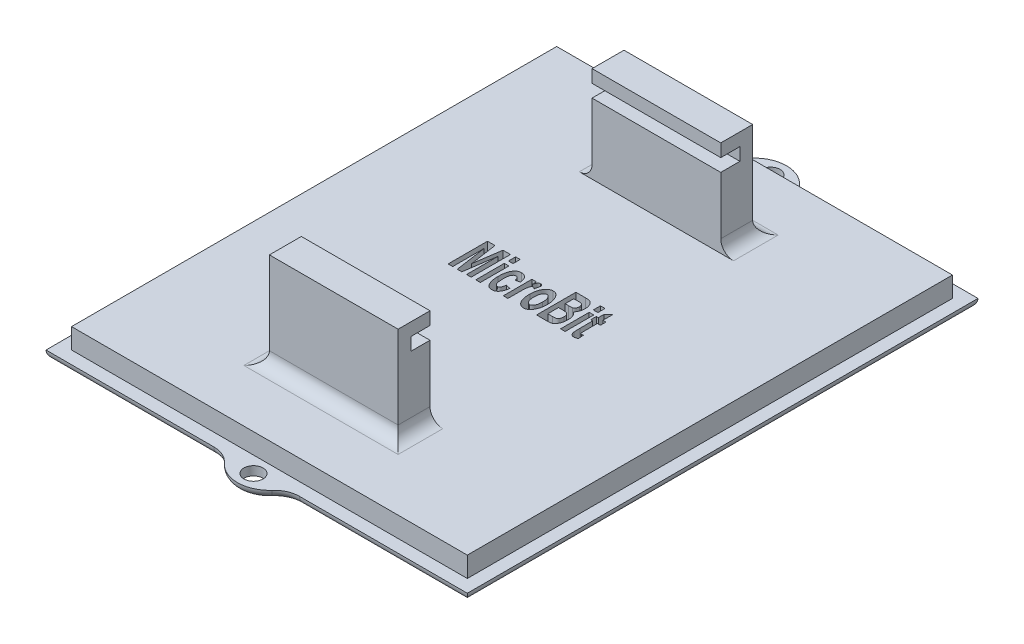
SolidWorks part; units mm, degrees
ref_plane "Front Plane" through (0, 0, 0) normal (0, 0, 1) x (1, 0, 0)
ref_plane "Top Plane" through (0, 0, 0) normal (0, 1, 0) x (1, 0, 0)
ref_plane "Right Plane" through (0, 0, 0) normal (1, 0, 0) x (0, 0, -1)
sketch "Sketch1" plane through (0, 0, 0) normal (0, 1, 0) x (1, 0, 0)
  line L0 (-31, 38) -> (31, 38)
  line L5 (-31, 38) -> (-31, -38)
  line L6 (-31, -38) -> (31, -38)
  line L7 (31, 38) -> (31, -38)
  point P11 (-31, 0)
  point P12 (0, -38)
  dimension "D3" = 76
  dimension "D4" = 62
extrude "Boss-Extrude1" add sketch "Sketch1" along normal blind 4.575
sketch "Sketch11" plane through (0, 0, 0) normal (0, -1, 0) x (-1, 0, 0)
  line L0 (-31, 38) -> (31, 38) construction
  line L1 (-33, -40) -> (33, -40)
  line L2 (-33, -40) -> (-33, 40)
  line L3 (-33, 40) -> (33, 40)
  line L4 (33, -40) -> (33, 40)
  line L5 (-31, -38) -> (-31, 38) construction
  line L6 (31, -38) -> (-31, -38) construction
  line L13 (31, 38) -> (31, -38) construction
  dimension "D1" = 2
  dimension "D2" = 2
  dimension "D3" = 2
  dimension "D4" = 2
extrude "Boss-Extrude5" add sketch "Sketch11" against normal blind 1.4
sketch "Sketch4" plane through (0, 0, 0) normal (0, 1, 0) x (1, 0, 0)
  line L2 (-31, -38) -> (31, -38) construction
  line L3 (33, -40) -> (-33, -40) construction
  line L5 (-6.7082, -40) -> (6.7082, -40)
  arc A3 (-6.7082, -40) -> (-3.7268, -41.3333) centre (-6.7082, -44) cw
  arc A4 (-3.7268, -41.3333) -> (3.7268, -41.3333) centre (0, -38) ccw
  arc A5 (3.7268, -41.3333) -> (6.7082, -40) centre (6.7082, -44) cw
  dimension "D1" = 5
  dimension "D4" = 4
extrude "Boss-Extrude3" add sketch "Sketch4" along normal blind 1.4
sketch "Sketch12" plane through (0, 1.4, 0) normal (0, 1, 0) x (1, 0, 0)
  line L0 (0, -38) -> (0, -43) construction
  line L1 (-31, -38) -> (31, -38) construction
  arc A0 (-3.7268, -41.3333) -> (3.7268, -41.3333) centre (0, -38) ccw construction
  circle A1 centre (0, -40.5) radius 1.5
  dimension "D1" = 3
extrude "Cut-Extrude3" cut sketch "Sketch12" against normal up to next
mirror "Mirror1" about plane through (0, 0, 0) normal (0, 0, 1) of "Cut-Extrude3", "Boss-Extrude3"
fillet "Fillet1" radius 1.4 12 edges at (19.8541, 0, -40) (5.0752, 0, -40.3485) (0, 0, -43) (-5.0752, 0, -40.3485) (-19.8541, 0, -40) (-33, 0, 0) (-19.8541, 0, 40) (-5.0752, 0, 40.3485) (0, 0, 43) (5.0752, 0, 40.3485) (19.8541, 0, 40) (33, 0, 0)
sketch "Sketch5" plane through (0, 4.575, 0) normal (0, 1, 0) x (1, 0, 0)
  line L0 (-15, 0) -> (15, 0) construction
  text T0 "MicroBit" font "Arial Narrow" height in points 24
  point P6 (0, 0)
  dimension "D1" = 30
extrude "Letters" cut sketch "Sketch5" against normal blind 2
sketch "Sketch21" plane through (0, 4.575, 0) normal (0, 1, 0) x (1, 0, 0)
  line L1 (-21.1498, 24.9347) -> (20.8502, 24.9347)
  line L2 (-21.1498, 24.9347) -> (-21.1498, -26.5653)
  line L3 (-21.1498, -26.5653) -> (20.8502, -26.5653)
  line L4 (20.8502, 24.9347) -> (20.8502, -26.5653)
  line L5 (-21.1498, 24.9347) -> (20.8502, -26.5653) construction
  line L6 (-21.1498, -26.5653) -> (20.8502, 24.9347) construction
  line L7 (-10.2291, -22.7722) -> (9.9294, -22.7722)
  line L8 (-10.2291, -22.7722) -> (-10.2291, -27.7722)
  line L9 (-10.2291, -27.7722) -> (9.9294, -27.7722)
  line L10 (9.9294, -22.7722) -> (9.9294, -27.7722)
  line L11 (-10.2291, -22.7722) -> (9.9294, -27.7722) construction
  line L12 (-10.2291, -27.7722) -> (9.9294, -22.7722) construction
  point P4 (-0.1498, -0.8153)
  point P9 (-0.1498, -25.2722)
  dimension "D1" = 42
  dimension "D2" = 51.5
  dimension "D3" = 5
extrude "Boss-Extrude8" add sketch "Sketch21" along normal blind 15 contours L9 L10 L7 L8
sketch "Sketch33" plane through (9.9294, 0, 0) normal (1, 0, 0) x (0, 0, -1)
  line L0 (-22.7722, 19.575) -> (-22.7722, 4.575) construction
  line L1 (-22.7722, 17.575) -> (-25.7722, 17.575)
  line L2 (-22.7722, 17.575) -> (-22.7722, 15.575)
  line L3 (-22.7722, 15.575) -> (-25.7722, 15.575)
  line L4 (-25.7722, 17.575) -> (-25.7722, 15.575)
  line L5 (-22.7722, 17.575) -> (-25.7722, 15.575) construction
  line L6 (-22.7722, 15.575) -> (-25.7722, 17.575) construction
  line L7 (-22.7722, 4.575) -> (-27.7722, 4.575) construction
  point P4 (-24.2722, 16.575)
  dimension "D1" = 2
  dimension "D2" = 3
  dimension "D3" = 11
extrude "Cut-Extrude7" cut sketch "Sketch33" against normal blind 25
mirror "Mirror2" about plane through (0, 0, 0) normal (0, 0, 1) of "Cut-Extrude7", "Boss-Extrude8"
fillet "Fillet2" radius 2 6 edges at (9.9294, 4.575, 25.2722) (-10.2291, 4.575, 25.2722) (-0.1498, 4.575, 27.7722) (-10.2291, 4.575, -25.2722) (-0.1498, 4.575, -27.7722) (9.9294, 4.575, -25.2722)
